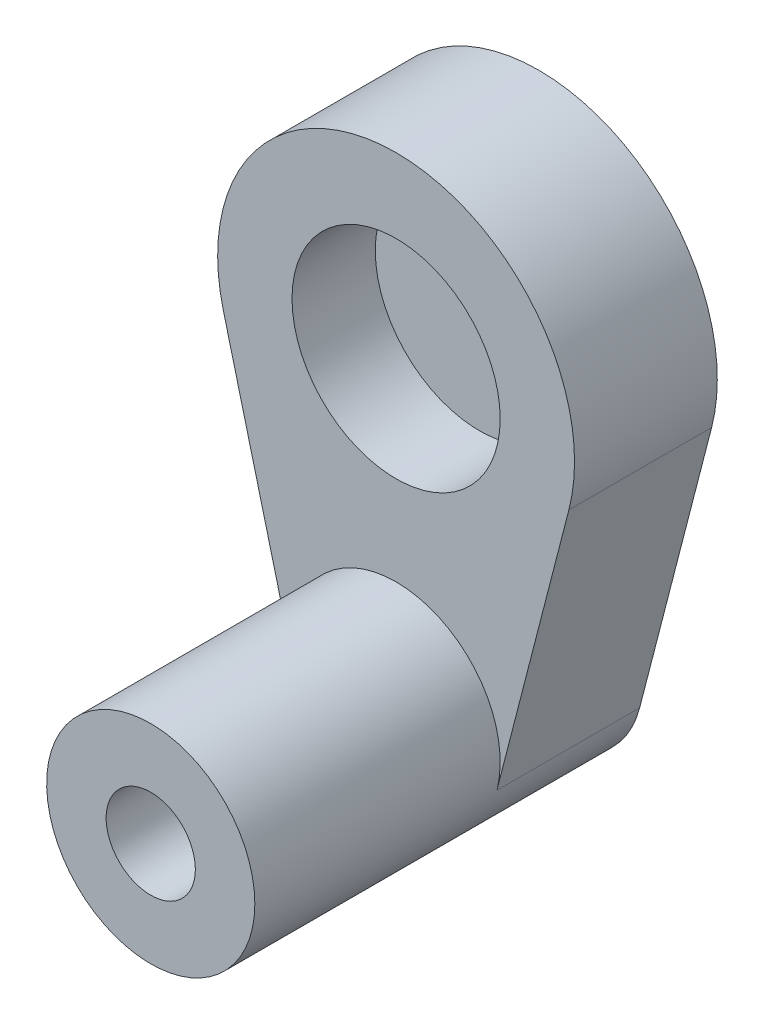
SolidWorks part; units mm, degrees
ref_plane "Front Plane" through (0, 0, 0) normal (0, 0, 1) x (1, 0, 0)
ref_plane "Top Plane" through (0, 0, 0) normal (0, 1, 0) x (1, 0, 0)
ref_plane "Right Plane" through (0, 0, 0) normal (1, 0, 0) x (0, 0, -1)
sketch "Sketch1" plane through (0, 0, 0) normal (0, 0, 1) x (1, 0, 0)
  circle A0 centre (0, 0) radius 1.5
  circle A1 centre (0, 0) radius 3.5
  dimension "D1" = 3
  dimension "D2" = 7
extrude "Boss-Extrude1" add sketch "Sketch1" along normal blind 8.25
sketch "Sketch2" plane through (0, 0, 0) normal (0, 0, -1) x (-1, 0, 0)
  line L0 (-5.8095, 8.5) -> (-3.3889, -0.875)
  line L1 (5.8095, 8.5) -> (3.3889, -0.875)
  circle A0 centre (0, 10) radius 3.5
  circle A1 centre (0, 10) radius 6
  circle A2 centre (0, 0) radius 3.5 construction
  arc A3 (-3.3889, -0.875) -> (3.3889, -0.875) centre (0, 0) ccw
  point P11 (0, 0)
  point P12 (0, 0)
  circle M4 centre (0, 0) radius 3.5
  circle M5 centre (0, 0) radius 1.5
  dimension "D1" = 7
  dimension "D2" = 12
  dimension "D3" = 10
extrude "Boss-Extrude2" add sketch "Sketch2" along normal blind 2.8 contours A1 L0 L1 M4 | A1 A0 | M4 M5 | M5 region at (0, 3.6774, 0) region at (0.7346, 15.7838, 0) region at (0.4285, 3.3739, 0) region at (0, 0, 0)
extrude "Boss-Extrude3" add sketch "Sketch2<3>" along normal blind 2 from surface contours A1 A0 | A1 L0 L1 M4 | M4 M5 | A0 | M5 region at (0, 3.6774, 0) region at (0.7346, 15.7838, 0) region at (0.4285, 3.3739, 0) region at (0, 10, 0) region at (0, 0, 0) starting at face at (0, 5.0312, -2.8)
sketch "Sketch2<3>" plane through (0, 0, 0) normal (0, 0, -1) x (-1, 0, 0) same geometry as "Sketch2"
